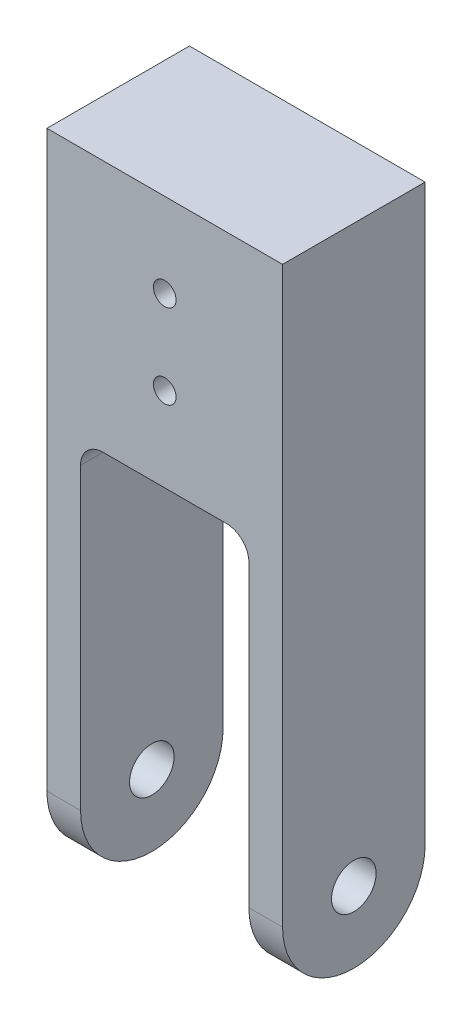
SolidWorks part; units mm, degrees
ref_plane "前基準面" through (0, 0, 0) normal (0, 0, 1) x (1, 0, 0)
ref_plane "上基準面" through (0, 0, 0) normal (0, 1, 0) x (1, 0, 0)
ref_plane "右基準面" through (0, 0, 0) normal (1, 0, 0) x (0, 0, -1)
sketch "草圖1" plane through (0, 0, 0) normal (0, 1, 0) x (1, 0, 0)
  line L1 (-21, -12.7) -> (21, -12.7)
  line L2 (-21, -12.7) -> (-21, 12.7)
  line L3 (-21, 12.7) -> (21, 12.7)
  line L4 (21, -12.7) -> (21, 12.7)
  line L5 (-21, -12.7) -> (21, 12.7) construction
  line L6 (-21, 12.7) -> (21, -12.7) construction
  point P0 (0, 0)
  dimension "D1" = 42
  dimension "D2" = 25.4
extrude "填料-伸長1" add sketch "草圖1" along normal blind 70
sketch "草圖2" plane through (21, 0, 0) normal (1, 0, 0) x (0, 0, -1)
  line L0 (0, 70) -> (0, 0) construction
  line L1 (-12.7, 70) -> (12.7, 70) construction
  line L2 (-12.7, 0) -> (12.7, 0) construction
  line L3 (-8.75, 70) -> (-8.75, 0)
  line L4 (-8.75, 70) -> (8.75, 70)
  line L5 (-8.75, 0) -> (8.75, 0)
  line L6 (8.75, 70) -> (8.75, 0)
  line L7 (-8.75, 70) -> (8.75, 0) construction
  line L8 (-8.75, 0) -> (8.75, 70) construction
  point P6 (0, 35)
  point P8 (0, 35)
  dimension "D1" = 17.5
sketch "草圖3" plane through (-21, 0, 0) normal (-1, 0, 0) x (0, 0, 1)
  line L0 (0, 0) -> (0, 70) construction
  line L1 (-12.7, 0) -> (12.7, 0) construction
  line L2 (-12.7, 70) -> (12.7, 70) construction
  line L3 (8.75, 70) -> (8.75, 0)
  line L4 (8.75, 70) -> (-8.75, 70)
  line L5 (8.75, 0) -> (-8.75, 0)
  line L6 (-8.75, 70) -> (-8.75, 0)
  line L7 (8.75, 70) -> (-8.75, 0) construction
  line L8 (8.75, 0) -> (-8.75, 70) construction
  point P6 (0, 35)
  point P8 (0, 35)
  dimension "D1" = 17.5
sketch "草圖5" plane through (0, 0, 0) normal (0, -1, 0) x (1, 0, 0)
  line L0 (21, -12.7) -> (-21, -12.7) construction
  line L1 (-21, 12.7) -> (-15, 12.7)
  line L2 (-21, 12.7) -> (-21, -12.7)
  line L3 (-21, -12.7) -> (-15, -12.7)
  line L4 (-15, 12.7) -> (-15, -12.7)
  line L6 (21, 12.7) -> (15, 12.7)
  line L7 (21, 12.7) -> (21, -12.7)
  line L8 (21, -12.7) -> (15, -12.7)
  line L9 (15, 12.7) -> (15, -12.7)
  dimension "D1" = 6
  dimension "D2" = 6
extrude "填料-伸長5" add sketch "草圖5" along normal blind 70
sketch "草圖6" plane through (-21, 0, 0) normal (-1, 0, 0) x (0, 0, 1)
  line L0 (0, -70) -> (0, 70) construction
  line L2 (12.7, -70) -> (-12.7, -70) construction
  line L3 (-12.7, 70) -> (12.7, 70) construction
  circle A0 centre (0, -57.3) radius 3.9688
  dimension "D1" = 7.9375
  dimension "D2" = 12.7
extrude "除料-伸長2" cut sketch "草圖6" against normal through all
fillet "圓角6" radius 4 2 edges at (15, 0, 0)
hole_wizard "#10-32 螺紋孔1" positions "草圖8" profile "草圖7" tap size "#10-32" standard "Ansi 英吋" end condition through all
sketch "草圖8" plane through (0, 0, 12.7) normal (0, 0, 1) x (1, 0, 0)
  line L0 (0, 70) -> (0, 0) construction
  line L1 (-21, 70) -> (21, 70) construction
  line L2 (-11, 0) -> (11, 0) construction
  point P0 (0, 30)
  point P11 (0, 15)
  dimension "D1" = 30
  dimension "D2" = 15
cosmetic thread "鑽孔螺紋1" parameters "D2"=4.826
cosmetic thread "鑽孔螺紋2" parameters "D2"=4.826
sketch "草圖7" plane through (0, 30, 12.7) normal (1, 0, 0) x (0, -1, 0)
  line L0 (0, 0) -> (0, 25.4)
  line L1 (0, 25.4) -> (2.0193, 25.4)
  line L2 (2.0193, 25.4) -> (2.0193, 0)
  line L5 (2.0193, 0) -> (0, 0)
  line L11 (0, -6.35) -> (0, 107.95) construction
  dimension "貫穿螺孔鑽直徑" = 4.0386
  dimension "貫穿螺孔鑽深度" = 25.4
fillet "圓角7" radius 12.7 4 edges at (18, -70, 12.7) (18, -70, -12.7) (-18, -70, 12.7) (-18, -70, -12.7)
sketch "草圖9" plane through (0, 0, 12.7) normal (0, 0, 1) x (1, 0, 0)
  line L0 (-21, 70) -> (-21, -57.3) construction
  line L1 (-21, 70) -> (21, 70)
  line L2 (-21, 70) -> (-21, 45)
  line L3 (-21, 45) -> (21, 45)
  line L4 (21, 70) -> (21, 45)
  line L5 (-21, 70) -> (21, 70) construction
  line L6 (21, 70) -> (21, -57.3) construction
  circle A0 centre (0, 30) radius 2.0193 construction
  dimension "D1" = 15
extrude "除料-伸長3" cut sketch "草圖9" against normal through all
